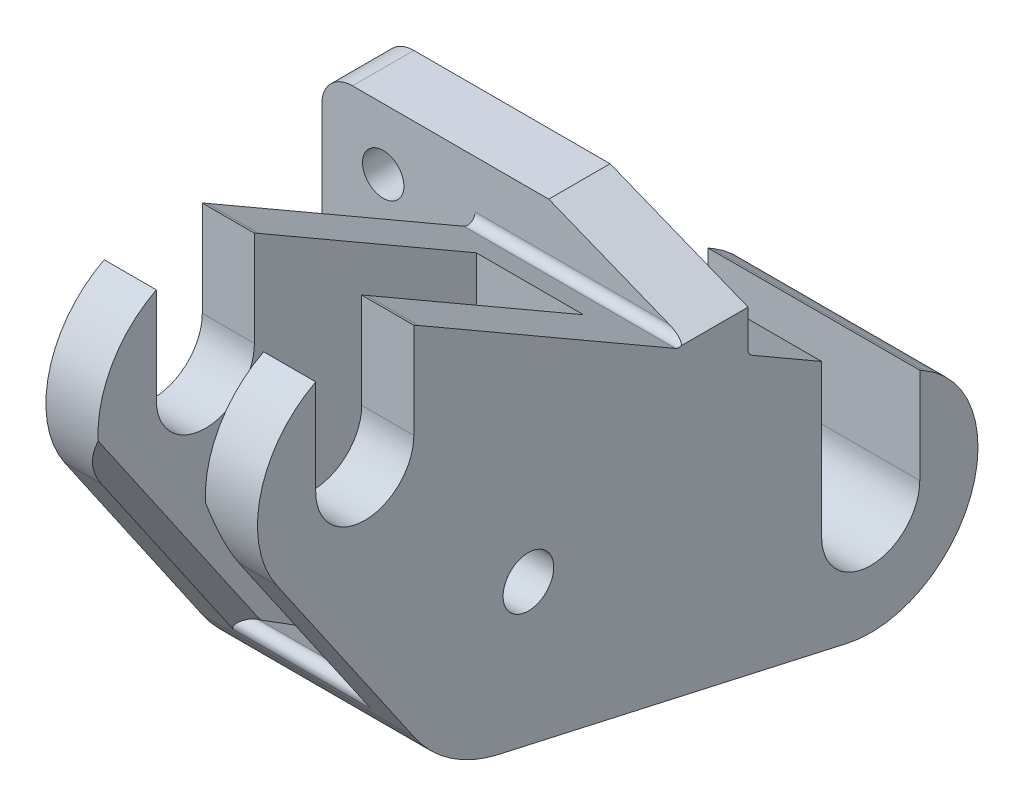
SolidWorks part; units mm, degrees
ref_plane "Front Plane" through (0, 0, 0) normal (0, 0, 1) x (1, 0, 0)
ref_plane "Top Plane" through (0, 0, 0) normal (0, 1, 0) x (1, 0, 0)
ref_plane "Right Plane" through (0, 0, 0) normal (1, 0, 0) x (0, 0, -1)
ref_plane "Plane4" through (14, 0, 0) normal (1, 0, 0) x (0, 0, -1)
ref_plane "Plane5" through (7.1, 0, 0) normal (1, 0, 0) x (0, 0, -1)
sketch "Sketch1" plane through (14, 0, 0) normal (1, 0, 0) x (0, 0, -1)
  line L0 (3.5235, 220.1706) -> (3.2238, 220.3437)
  line L1 (-32.977, 233.1595) -> (-32.9759, 206.2902) construction
  line L2 (-29.777, 233.1595) -> (-29.777, 239.3852)
  line L3 (-38.7467, 229.1957) -> (-29.7246, 216.0632)
  line L4 (-24.2736, 212.3771) -> (-1.5062, 207.2776)
  line L5 (-36.177, 233.1595) -> (-36.177, 239.3852)
  line L6 (3.2238, 214.1083) -> (3.2238, 220.3437)
  line L7 (-3.1762, 214.1083) -> (-3.1762, 224.0384)
  line L8 (-3.1762, 224.0384) -> (-29.4773, 239.2218)
  arc A0 (-36.177, 239.3852) -> (-38.7467, 229.1957) centre (-32.977, 233.1595) ccw
  arc A1 (3.2238, 214.1083) -> (-3.1762, 214.1083) centre (0.0238, 214.1083) cw
  arc A2 (-29.777, 233.1595) -> (-36.177, 233.1595) centre (-32.977, 233.1595) cw
  arc A3 (-1.5062, 207.2776) -> (3.5235, 220.1706) centre (0.0238, 214.1083) ccw
  arc A4 (-29.4773, 239.2218) -> (-29.777, 239.3852) centre (-32.977, 233.1595) ccw
  circle A6 centre (-22.3065, 221.1595) radius 1.65
  arc A7 (-29.7246, 216.0632) -> (-24.2736, 212.3771) centre (-22.3065, 221.1595) ccw
  dimension "D1" = 3.3
  dimension "D2" = 6.4
  dimension "D3" = 7
  dimension "D8" = 9
  dimension "D4" = 38.1051
  dimension "D5" = 60
  dimension "D6" = 10.67
  dimension "D7" = 12
extrude "Boss-Extrude1" add sketch "Sketch1" against normal blind 13.8
sketch "Sketch2" plane through (0.2, 0, 0) normal (-1, 0, 0) x (0, 0, 1)
  line L0 (24.2736, 212.3771) -> (1.5062, 207.2776) construction
  line L1 (7.9762, 233.1083) -> (11.9762, 233.1083)
  line L2 (7.9762, 233.1083) -> (7.9762, 208.7267)
  line L3 (7.9762, 208.7267) -> (11.9762, 209.6227)
  line L4 (11.9762, 233.1083) -> (11.9762, 209.6227)
  circle A0 centre (-0.0238, 214.1083) radius 3.2 construction
  dimension "D1" = 12
  dimension "D3" = 19
  dimension "D2" = 4
extrude "Boss-Extrude2" add sketch "Sketch2" along normal blind 10 and the other way up to surface (13.8 mm away) other way up to face at (14, 221.1595, 23.9565)
ref_axis "Axis1" through (0.2, 214.1083, -0.0238) along (1, 0, 0)
sketch "Sketch3" plane through (0, 0, 7.9762) normal (0, 0, -1) x (-1, 0, 0)
  line L0 (-0.2, 207.1083) -> (-0.2, 220.1706) construction
  line L2 (-0.2, 214.1083) -> (-14, 214.1083) construction
  circle A0 centre (5.8, 229.1083) radius 1.35
  dimension "D2" = 2.7
  dimension "D1" = 6
  dimension "D3" = 15
extrude "Cut-Extrude1" cut sketch "Sketch3" against normal through all
chamfer "Chamfer1" distance 9 distance2 10 1 edges at (-9.8, 209.1747, 9.9762) first distance on face at (1.15, 209.501, 11.4331)
chamfer "Chamfer2" distance 3.6 distance2 9 1 edges at (14, 233.1083, 9.9762) first distance on face at (14, 221.1595, 23.9565)
fillet "Fillet1" radius 2 1 edges at (-9.8, 233.1083, 9.9762)
fillet "Fillet2" radius 0.5 1 edges at (7.1, 226.8094, 7.9762)
fillet "Fillet3" radius 0.5 1 edges at (7.1, 229.1186, 11.9762)
fillet "Fillet4" radius 1 1 edges at (0.2, 217.9124, 7.9762)
sketch "Sketch4" plane through (7.1, 0, 0) normal (1, 0, 0) x (0, 0, -1)
  line L0 (-39.0851, 223.4157) -> (-26.0245, 215.2285)
  line L1 (-15.3065, 221.1595) -> (-15.3065, 244.6595)
  line L2 (-15.3065, 244.6595) -> (-32.977, 244.6595)
  arc A0 (-26.0245, 215.2285) -> (-15.3065, 221.1595) centre (-22.3065, 221.1595) ccw
  circle A1 centre (-22.3065, 221.1595) radius 1.65 construction
  circle A2 centre (-22.3065, 221.1595) radius 5 construction
  circle A3 centre (-32.977, 233.1595) radius 9.5 construction
  arc A4 (-32.977, 244.6595) -> (-39.0851, 223.4157) centre (-32.977, 233.1595) ccw
  dimension "D1" = 2
  dimension "D2" = 19
  dimension "D3" = 10
  dimension "D4" = 2
extrude "Cut-Extrude2" cut sketch "Sketch4" against normal blind 3.5 and the other way blind 3.5
sketch "Sketch5" plane through (10.6, 0, 0) normal (-1, 0, 0) x (0, 0, 1)
  circle A0 centre (22.3065, 221.1595) radius 2.6
  circle A1 centre (22.3065, 221.1595) radius 1.629
  dimension "D1" = 5.2
extrude "Boss-Extrude3" add sketch "Sketch5" along normal blind 1.4
sketch "Sketch6" plane through (3.6, 0, 0) normal (1, 0, 0) x (0, 0, -1)
  circle A0 centre (-22.3065, 221.1595) radius 2.6
  circle A1 centre (-22.3065, 221.1595) radius 1.65
  dimension "D1" = 5.2
extrude "Boss-Extrude4" add sketch "Sketch6" along normal blind 1.4
fillet "Fillet5" radius 0.5 1 edges at (7.1, 218.671, 31.5162)
chamfer "Chamfer3" distance 1 angle 45 2 edges at (10.6, 222.9396, 34.4487) (3.6, 222.9396, 34.4487) tangent propagation no
